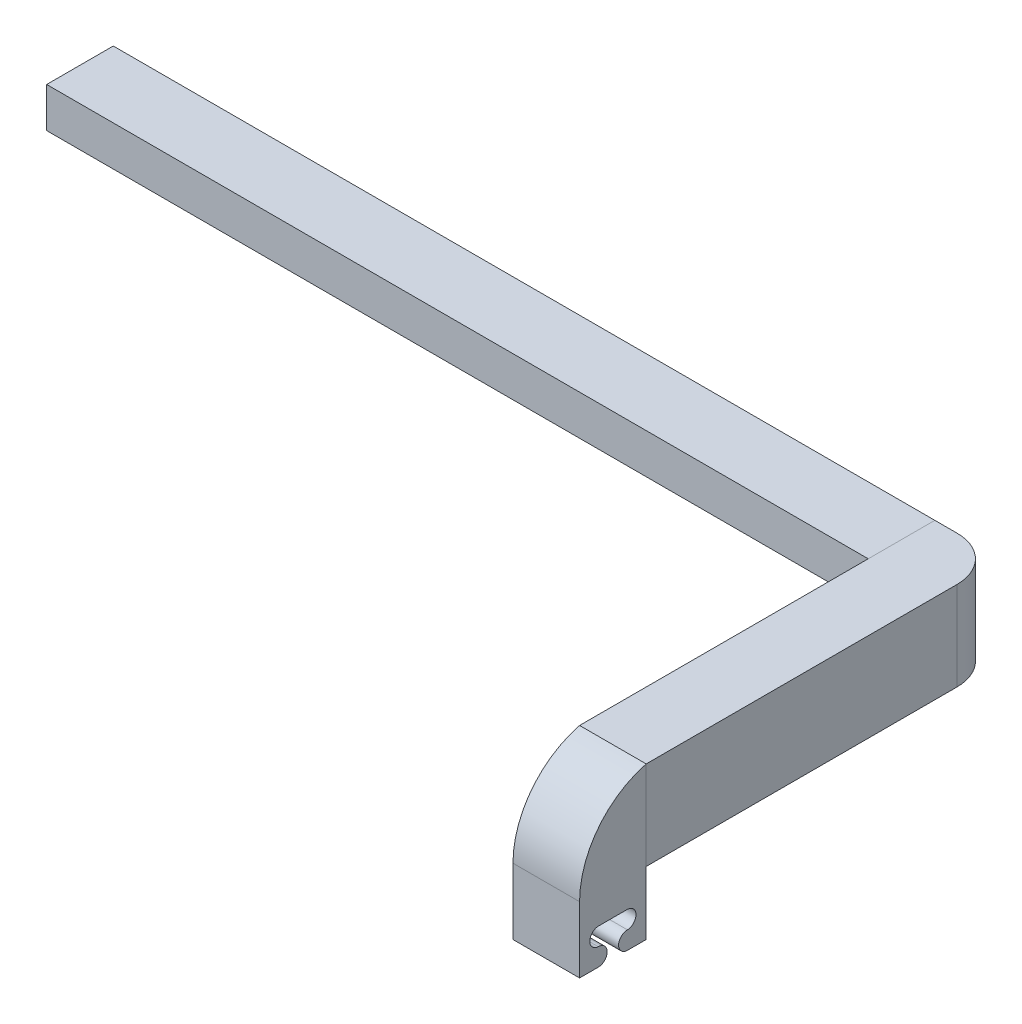
SolidWorks part; units mm, degrees
ref_plane "Front Plane" through (0, 0, 0) normal (0, 0, 1) x (1, 0, 0)
ref_plane "Top Plane" through (0, 0, 0) normal (0, 1, 0) x (1, 0, 0)
ref_plane "Right Plane" through (0, 0, 0) normal (1, 0, 0) x (0, 0, -1)
sketch "Sketch1" plane through (0, 0, 0) normal (0, 0, 1) x (1, 0, 0)
  line L6 (48.0544, -51.8775) -> (48.2794, -51.8775)
  line L19 (51.6669, -45.8775) -> (59.1669, -45.8775)
  line L20 (51.6669, -45.8775) -> (44.6669, -45.8775) construction
  line L21 (41.9169, -64.1275) -> (54.4169, -64.1275)
  line L22 (41.9169, -64.1275) -> (41.9169, -69.3775)
  line L24 (54.4169, -64.1275) -> (54.4169, -69.3775)
  line L25 (59.1669, -69.3775) -> (37.1669, -69.3775)
  line L28 (37.1669, -45.8775) -> (44.6669, -45.8775)
  line L32 (44.6669, -45.8775) -> (51.6669, -45.8775)
  line L33 (37.1669, -45.8775) -> (37.1669, -69.3775)
  line L34 (59.1669, -45.8775) -> (59.1669, -69.3775)
  line L35 (59.1669, -50.8775) -> (37.1669, -50.8775) construction
  line L36 (48.1669, -50.8775) -> (48.1669, 64.3396) construction
  line L38 (48.0544, -49.8775) -> (48.2794, -49.8775)
  arc A0 (48.2794, -51.8775) -> (48.2794, -49.8775) centre (52.6669, -50.8775) ccw
  arc A1 (48.0544, -49.8775) -> (48.0544, -51.8775) centre (43.6669, -50.8775) ccw
  point P0 (0, 0)
  point P9 (51.5, -66.7525)
  point P11 (41.9169, -66.7525)
  dimension "D7" = 9
  dimension "D3" = 12.5
  dimension "D4" = 5
  dimension "D8" = 7.5
  dimension "D9" = 7.5
  dimension "D10" = 23.5
  dimension "D11" = 5.25
  dimension "D12" = 4.75
  dimension "D13" = 9
  dimension "D5" = 22
extrude "pusher base" add sketch "Sketch1" along normal blind 15 contours L32 L28 L19 A1 A0 L21 L24 L22 region at (48.1669, -58.4331, 0)
sketch "Sketch3" plane through (0, -64.1275, 0) normal (0, -1, 0) x (1, 0, 0)
  line L0 (48.1669, 15) -> (48.1669, 0) construction
  line L1 (41.9169, 15) -> (54.4169, 15) construction
  line L2 (41.9169, 0) -> (54.4169, 0) construction
  circle A0 centre (48.1669, 7.5) radius 1.95
  point P10 (48.1669, 7.5)
  dimension "D1" = 3.9
extrude "screw hole" cut sketch "Sketch3" against normal blind 7.5
ref_plane "Plane1" through (0, 0, 7.5) normal (0, 0, 1) x (1, 0, 0)
sketch "Sketch6" plane through (0, 0, 7.5) normal (0, 0, 1) x (1, 0, 0)
  line L0 (41.9169, -64.1275) -> (54.4169, -64.1275) construction
  line L5 (37.1669, -45.8775) -> (59.1669, -45.8775) construction
  line L6 (44.4169, -25.6275) -> (51.9169, -25.6275)
  line L11 (44.4169, -25.6275) -> (44.4169, -45.8775)
  line L12 (44.4169, -45.8775) -> (51.9169, -45.8775)
  line L13 (51.9169, -25.6275) -> (51.9169, -45.8775)
  line L14 (48.1669, -64.1275) -> (48.1669, -27.6275) construction
  line L15 (51.9169, -25.6275) -> (44.4169, -25.6275)
  line L16 (51.9169, -25.6275) -> (51.9169, -15.6275)
  line L17 (51.9169, -15.6275) -> (44.4169, -15.6275)
  line L18 (44.4169, -25.6275) -> (44.4169, -15.6275)
  point P2 (48.1669, -25.6275)
  point P8 (48.1669, -45.8775)
  dimension "D1" = 7.5
  dimension "D3" = 7.5
  dimension "D4" = 10
  dimension "D5" = 38.5
extrude "pusher head" add sketch "Sketch6" along normal mid plane 7.5 contours L18 L15 L6 L16 L17 | L13 L6 L12 | L11 L12 L6 region at (48.1669, -20.6275, 7.5) region at (48.1669, -35.7525, 7.5)
fillet "Fillet1" radius 2 2 edges at (48.1669, -45.8775, 0) (48.1669, -45.8775, 15)
sketch "Sketch12" plane through (44.4169, 0, 0) normal (-1, 0, 0) x (0, 0, 1)
  line L0 (7.5, -15.6275) -> (7.5, -45.8775) construction
  line L1 (11.25, -15.6275) -> (3.75, -15.6275) construction
  line L2 (11.25, -45.8775) -> (3.75, -45.8775) construction
  line L3 (3.75, -30.7525) -> (11.25, -30.7525) construction
  line L4 (3.75, -45.8775) -> (3.75, -15.6275) construction
  line L5 (11.25, -45.8775) -> (11.25, -15.6275) construction
  line L6 (5.8585, -32.7525) -> (3.75, -32.7525)
  line L7 (5.8585, -28.7525) -> (9.1415, -28.7525)
  line L8 (9.1415, -32.7525) -> (11.25, -32.7525)
  line L9 (3.75, -32.7025) -> (5.8585, -32.7025)
  line L10 (11.25, -32.7025) -> (9.1415, -32.7025)
  arc A0 (5.8585, -32.7525) -> (5.8585, -30.7525) centre (5.8585, -31.7525) ccw
  arc A1 (5.8585, -28.7525) -> (5.8585, -30.7525) centre (5.8585, -29.7525) ccw
  arc A2 (9.1415, -32.7525) -> (9.1415, -30.7525) centre (9.1415, -31.7525) cw
  arc A3 (9.1415, -28.7525) -> (9.1415, -30.7525) centre (9.1415, -29.7525) cw
  arc A4 (5.8585, -30.7525) -> (5.8585, -32.7025) centre (5.8585, -31.7275) cw
  arc A5 (9.1415, -30.7525) -> (9.1415, -32.7025) centre (9.1415, -31.7275) ccw
  arc A6 (5.8585, -30.7525) -> (5.8585, -28.7525) centre (5.9027, -29.7525) cw
  arc A7 (9.1415, -30.7525) -> (9.1415, -28.7525) centre (9.0973, -29.7525) ccw
  point P25 (7.5, -28.7525)
  line M4 (3.75, -15.6275) -> (3.75, -45.8775)
  line M5 (3.75, -45.8775) -> (11.25, -45.8775)
  line M6 (11.25, -45.8775) -> (11.25, -15.6275)
  dimension "D1" = 2
  dimension "D2" = 0.05
extrude "Cut-Extrude1" cut sketch "Sketch12" against normal blind 7.5 contours A2 A7 L7 A6 A0 L6 L8 M4 M5 M6 region at (44.4169, -38.2639, 7.5)
sketch "Sketch9" plane through (51.9169, 0, 0) normal (1, 0, 0) x (0, 0, -1)
  line L1 (-3.75, -15.6275) -> (36.25, -15.6275)
  line L2 (-3.75, -15.6275) -> (-3.75, -25.6275)
  line L3 (-3.75, -25.6275) -> (36.25, -25.6275)
  line L4 (36.25, -15.6275) -> (36.25, -25.6275)
  point P5 (0, 0)
  point P6 (-0.7902, -17.2147)
  point P7 (0, 0)
  dimension "D1" = 10
  dimension "D2" = 40
extrude "Boss-Extrude1" add sketch "Sketch9" against normal blind 7.5
sketch "Sketch10" plane through (0, 0, -36.25) normal (0, 0, -1) x (-1, 0, 0)
  line L1 (-44.4169, -15.6275) -> (48.0831, -15.6275)
  line L2 (-44.4169, -15.6275) -> (-44.4169, -20.1275)
  line L3 (-44.4169, -20.1275) -> (48.0831, -20.1275)
  line L4 (48.0831, -15.6275) -> (48.0831, -20.1275)
  point P5 (-43.0364, -16.2442)
  dimension "D1" = 4.5
  dimension "D2" = 92.5
extrude "Boss-Extrude2" add sketch "Sketch10" against normal blind 7.5
fillet "Fillet7" radius 10 1 edges at (48.1669, -15.6275, 11.25)
fillet "Fillet8" radius 5 1 edges at (51.9169, -20.6275, -36.25)
ref_plane "Plane2" through (0, 0, 25) normal (0, 0, 1) x (1, 0, 0)
sketch "Sketch13" plane through (0, -45.8775, 0) normal (0, 1, 0) x (1, 0, 0)
  line L1 (27.4181, -20.1115) -> (69.3456, -20.1115)
  line L2 (27.4181, -20.1115) -> (27.4181, 5.1417)
  line L3 (27.4181, 5.1417) -> (69.3456, 5.1417)
  line L4 (69.3456, -20.1115) -> (69.3456, 5.1417)
extrude "Cut-Extrude2" cut sketch "Sketch13" against normal blind 26
equation "\"PusherHeight\"=2"
equation "\"PusherWidth\"=11"
equation "\"PusherLongWidth\"=5"
equation "\"RodDiameter\"=0.5"
equation "\"HookLength\"=2.01152"
equation "\"HookHeight\"=0.999652"
equation "\"HookInnerLength\"=2"
equation "\"RodHeightDistance\"=0.4276"
equation "\"RodWidthDistance\"=0.75"
equation "\"PusherDepth\"=2"
equation "\"BuckleShaftDiameter\"=0.383646"
equation "\"BeltBuckleDistance\"=1.5"
equation "\"DowelDiameter\"=0.9"
equation "\"D7@Sketch1\"=\"DowelDiameter\""
equation "\"RodSeperationDistance\"=3.98"
equation "\"BuckleNutDiameter\"=0.39"
equation "\"D1@Sketch3\"=\"BuckleNutDiameter\""
equation "\"belt hole width\"=1.4"
equation "\"pusher height\"=3.5175"
equation "\"pusher slot width\"=0.75"
equation "\"D1@Sketch6\"=\"pusher slot width\""
equation "\"pushing bar width\"=1"
equation "\"D4@Sketch6\"=\"pushing bar width\""
equation "\"doweltotop\"=0.5"
equation "\"D4@Sketch1\"=\"doweltotop\""
equation "\"dowel separation\"=0.9"
equation "\"D13@Sketch1\"=\"dowel separation\""
